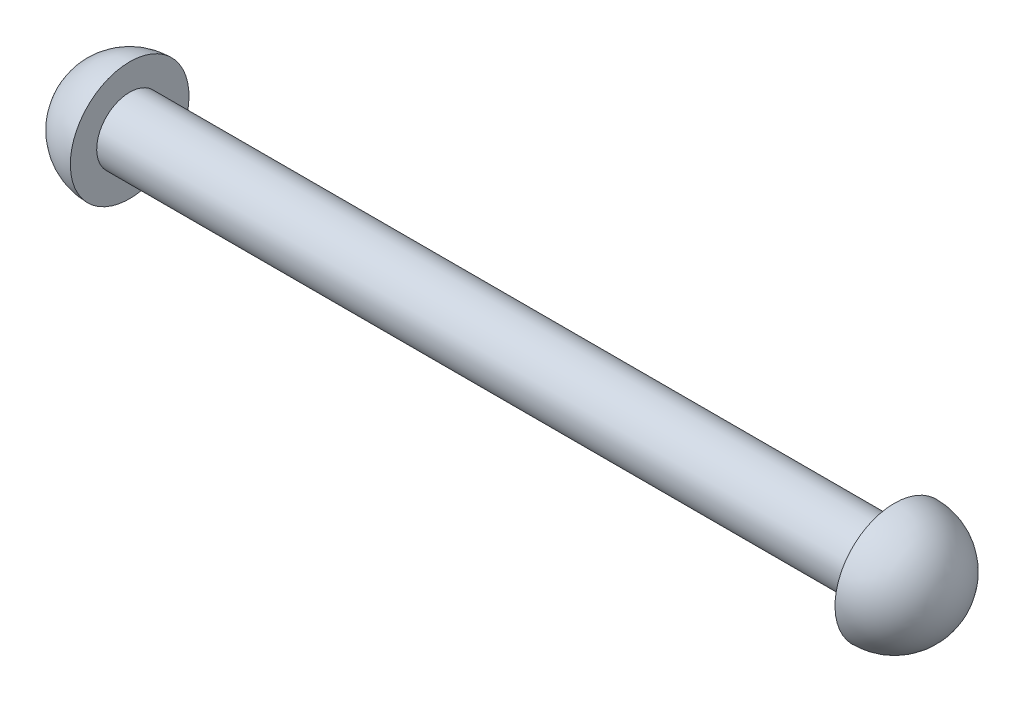
SolidWorks part; units mm, degrees
material "AISI 1020"
ref_plane "Front Plane" through (0, 0, 0) normal (0, 0, 1) x (1, 0, 0)
ref_plane "Top Plane" through (0, 0, 0) normal (0, 1, 0) x (1, 0, 0)
ref_plane "Right Plane" through (0, 0, 0) normal (1, 0, 0) x (0, 0, -1)
sketch "Sketch1" plane through (0, 0, 0) normal (0, 0, 1) x (1, 0, 0)
  line L0 (0, 8.89) -> (0, -2.54)
  line L1 (0, 0) -> (73.66, 0)
  line L2 (0, 0) -> (0, 6.35)
  line L3 (0, 6.35) -> (73.66, 6.35)
  line L4 (73.66, 0) -> (73.66, 6.35)
  line L5 (73.66, 8.89) -> (73.66, -2.54)
  line L6 (79.375, 3.175) -> (-5.715, 3.175) construction
  arc A0 (0, 8.89) -> (0, -2.54) centre (0, 3.175) ccw
  arc A1 (73.66, -2.54) -> (73.66, 8.89) centre (73.66, 3.175) ccw
  dimension "D3" = 5.715
  dimension "D1" = 73.66
  dimension "D2" = 6.35
revolve "Revolve1" add sketch "Sketch1" angle 360 about L6 region at (-2.4255, 5.6005, 0) region at (36.83, 4.7625, 0) region at (76.0855, 5.6005, 0)
